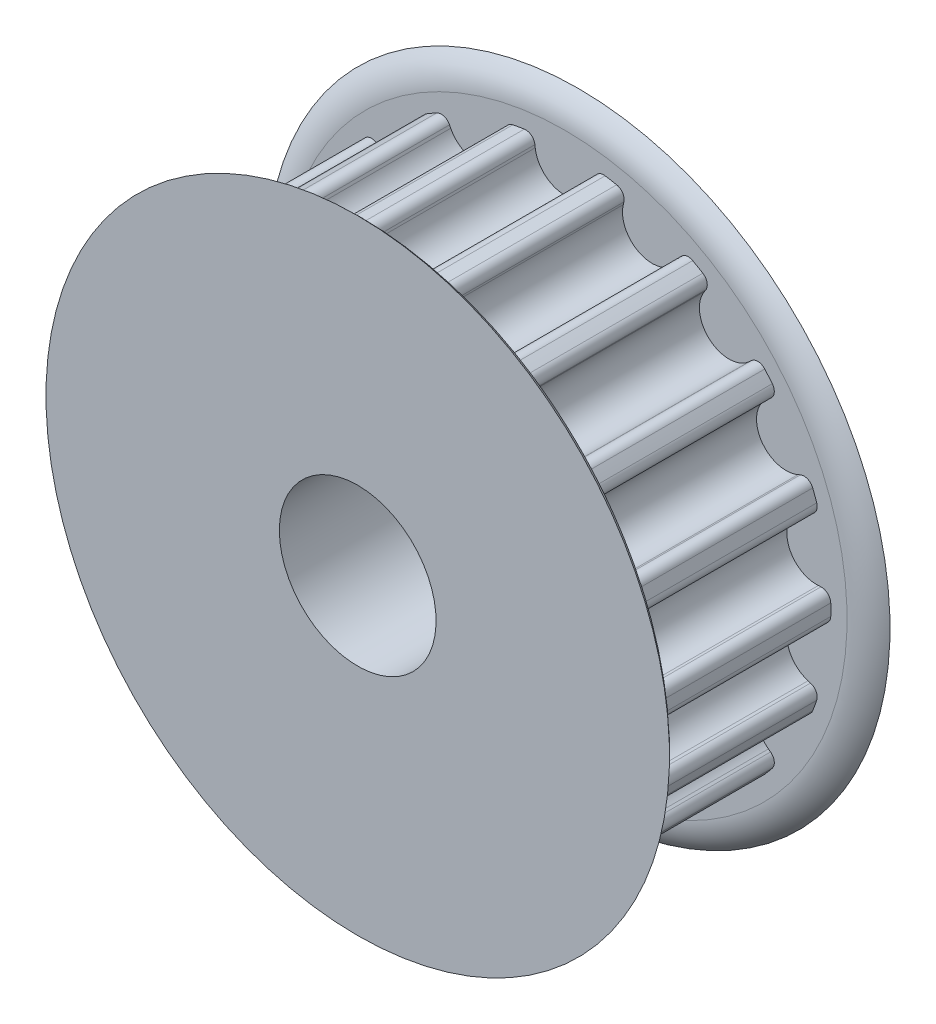
SolidWorks part; units mm, degrees
ref_plane "정면" through (0, 0, 0) normal (0, 0, 1) x (1, 0, 0)
ref_plane "윗면" through (0, 0, 0) normal (0, 1, 0) x (1, 0, 0)
ref_plane "우측면" through (0, 0, 0) normal (1, 0, 0) x (0, 0, -1)
sketch "스케치3" plane through (0, 0, 0) normal (0, 0, 1) x (1, 0, 0)
  line L0 (0, 0) -> (0, 13.7524) construction
  line L1 (0, 0) -> (-4.8991, 13.4601) construction
  line L3 (-1.5246, 13.0392) -> (-1.5971, 13.6594)
  line L4 (1.5246, 13.0392) -> (1.5971, 13.6594)
  circle A0 centre (0, 0) radius 14.3239 construction
  circle A2 centre (0, 0) radius 13.7524
  circle A3 centre (0, 13.2174) radius 1.535
  point P1 (0, 0)
  dimension "D2" = 28.6479
  dimension "D5" = 3.07
  dimension "D3" = 27.5049
  dimension "D1" = 20
  dimension "D4" = 2.07
extrude "보스-돌출2" add sketch "스케치3" along normal mid plane 10 contours A2
extrude "컷-돌출2" cut sketch "스케치3<3>" against normal through all both and the other way through all contours A3 A2 L3 | A2 A3 | A3 L4 A2 region at (0, 12.8309, 0) region at (-1.54, 13.5101, 0) region at (1.54, 13.5101, 0)
sketch "스케치3<3>" plane through (0, 0, 0) normal (0, 0, 1) x (1, 0, 0) same geometry as "스케치3"
fillet "필렛1" radius 0.48 2 edges at (1.5971, 13.6594, 0) (-1.5971, 13.6594, 0)
pattern_circular "원형 패턴1" count 18 over 360 about axis through (0, 0, 5) along (0, 0, -1) of "컷-돌출2", "필렛1"
sketch "스케치4" plane through (0, 0, -5) normal (0, 0, -1) x (-1, 0, 0)
  circle A0 centre (0, 0) radius 4.05
  dimension "D1" = 8.1
extrude "컷-돌출3" cut sketch "스케치4" against normal through all
sketch "스케치5" plane through (0, 0, -5) normal (0, 0, -1) x (-1, 0, 0)
  circle A0 centre (0, 0) radius 4.05 construction
  circle A1 centre (0, 0) radius 4.05
  circle A2 centre (0, 0) radius 7
  dimension "D1" = 14
extrude "보스-돌출3" add sketch "스케치5" along normal blind 5.7
hole_wizard "M3x0.5 탭을 위한 탭 드릴1" positions "스케치7" profile "스케치8" hole size "M3x0.5" standard "Ansi Metric" end condition through all
sketch "스케치7" plane through (0, 0, 0) normal (0, 1, 0) x (1, 0, 0)
  line L0 (0, 10.7) -> (0, 5) construction
  line L1 (7, 10.7) -> (-7, 10.7) construction
  line L2 (1.5246, 5) -> (-1.5246, 5) construction
  point P0 (0, 7.85)
  point P11 (0, 7.5)
sketch "스케치8" plane through (0, 0, -7.85) normal (1, 0, 0) x (0, 0, -1)
  line L0 (0, 0) -> (0, 13.5983)
  line L1 (0, 13.5983) -> (1.2, 13.5983)
  line L2 (1.2, 13.5983) -> (1.2, 0)
  line L5 (1.2, 0) -> (0, 0)
  line L11 (0, -6.35) -> (0, 107.95) construction
  dimension "관통 구멍 지름" = 2.4
  dimension "관통 구멍 깊이" = 13.5983
sketch "스케치9" plane through (0, 0, 0) normal (1, 0, 0) x (0, 0, -1)
  line L0 (-5.7, 16.1126) -> (-5.7, 4.05)
  line L1 (-5.7, 4.05) -> (-5, 4.05)
  line L2 (-5, 4.05) -> (-5, 14.5927)
  line L3 (5, 13.5927) -> (-5, 13.5927) construction
  line L4 (0, 0) -> (0, 13.5927) construction
  line L5 (5, 4.05) -> (5, 14.5927)
  line L6 (5.7, 4.05) -> (5, 4.05)
  line L7 (5.7, 16.1126) -> (5.7, 4.05)
  line L8 (-5, 4.05) -> (-5, -4.05) construction
  line L9 (5, -4.05) -> (5, 4.05) construction
  line L10 (0, 0) -> (-5, 0) construction
  arc A0 (-5, 14.5927) -> (-5.7, 16.1126) centre (-7, 14.5927) ccw
  arc A1 (5, 14.5927) -> (5.7, 16.1126) centre (7, 14.5927) cw
  point P16 (-8.4551, 0)
  dimension "D1" = 2
  dimension "D2" = 1
  dimension "D3" = 0.7
revolve "회전1" add sketch "스케치9" angle 360 about L10
equation "\"n\"= 18'number of teeth"
equation "\"D2@스케치3\"=5*\"n\"/(PI)"
equation "\"D1@스케치3\"=360/\"n\""
equation "\"D1@원형 패턴1\"=\"n\""
equation "\"D3@스케치3\"=\"D2@스케치3\"-2*0.225*2.54"
